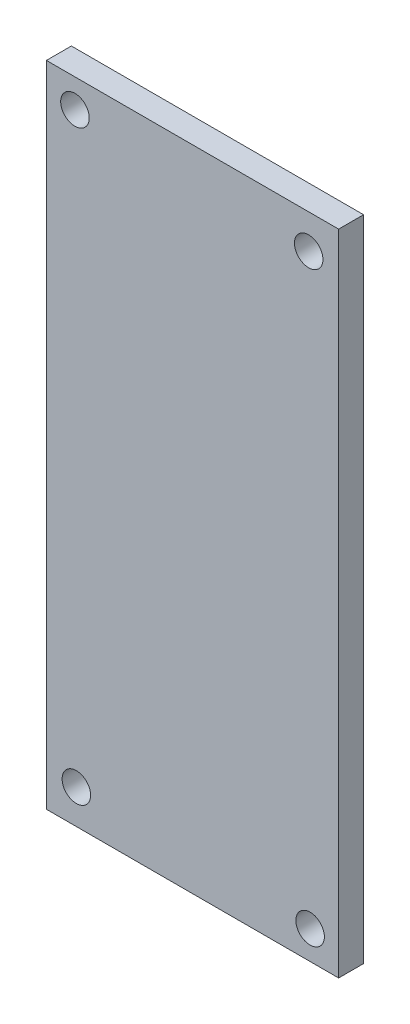
SolidWorks part; units mm, degrees
ref_plane "Front Plane" through (0, 0, 0) normal (0, 0, 1) x (1, 0, 0)
ref_plane "Top Plane" through (0, 0, 0) normal (0, 1, 0) x (1, 0, 0)
ref_plane "Right Plane" through (0, 0, 0) normal (1, 0, 0) x (0, 0, -1)
sketch "Sketch1" plane through (0, 0, 0) normal (0, 0, 1) x (1, 0, 0)
  line L0 (10.25, 0) -> (-10.25, 0) construction
  line L1 (-10.25, 22.75) -> (10.25, 22.75)
  line L2 (-10.25, 22.75) -> (-10.25, -22.75)
  line L3 (-10.25, -22.75) -> (10.25, -22.75)
  line L4 (10.25, 22.75) -> (10.25, -22.75)
  dimension "D1" = 20.5
  dimension "D2" = 45.5
extrude "Extrude1" add sketch "Sketch1" along normal blind 1.75
sketch "Sketch2" plane through (0, 0, 1.75) normal (0, 0, 1) x (1, 0, 0)
  line L0 (-10.25, -22.75) -> (10.25, -22.75) construction
  line L1 (-10.25, 22.75) -> (-10.25, -22.75) construction
  line L2 (10.25, 22.75) -> (-10.25, 22.75) construction
  line L3 (10.25, -22.75) -> (10.25, 22.75) construction
  circle A0 centre (8.25, -20.75) radius 1
  circle A1 centre (-8.25, 20.75) radius 1
  circle A2 centre (-8.15, -20.35) radius 1
  circle A3 centre (8.15, 20.35) radius 1
  dimension "D1" = 2
  dimension "D2" = 2
  dimension "D3" = 2
  dimension "D4" = 2
  dimension "D5" = 2
  dimension "D6" = 2
extrude "Cut-Extrude1" cut sketch "Sketch2" against normal up to surface (1.75 mm away) up to face at (0, 0, 0)
